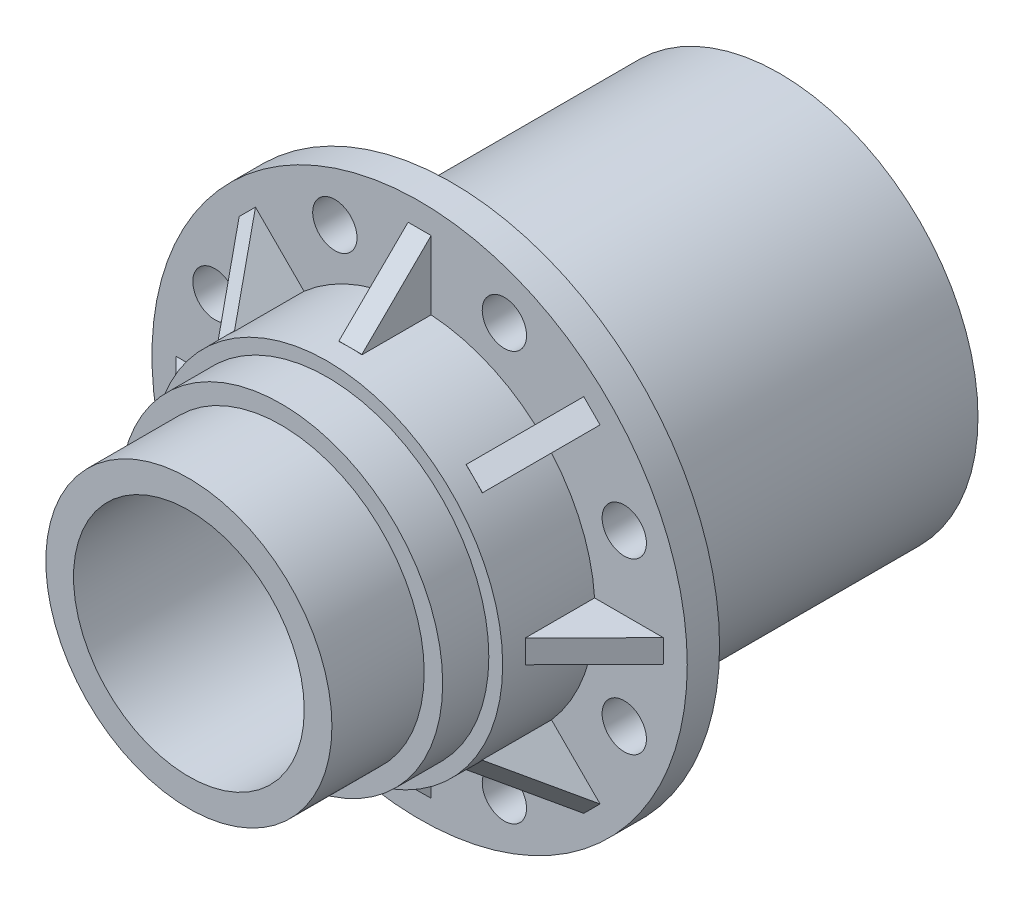
SolidWorks part; units mm, degrees
material "Plain Carbon Steel"
ref_plane "Front Plane" through (0, 0, 0) normal (1, 0, 0) x (0, 1, 0)
ref_plane "Top Plane" through (0, 0, 0) normal (0, 0, 1) x (0, 1, 0)
ref_plane "Right Plane" through (0, 0, 0) normal (0, 1, 0) x (-1, 0, 0)
sketch "Sketch2" plane through (0, 0, 0) normal (0, 0, 1) x (0, 1, 0)
  circle A0 centre (0, 0) radius 290
  circle A2 centre (0, 0) radius 215
  circle A3 centre (0, 0) radius 190
  circle A4 centre (0, 0) radius 155
  circle A5 centre (0, 0) radius 105
  circle A6 centre (0, 0) radius 80
  circle A7 centre (0, 0) radius 125
  dimension "D1" = 580
  dimension "D2" = 430
  dimension "D3" = 380
  dimension "D4" = 310
  dimension "D5" = 210
  dimension "D6" = 160
  dimension "D7" = 250
extrude "Boss-Extrude1" add sketch "Sketch2" against normal blind 390 contours A2 A3 | A3 A4 region at (0, -208.9189, 0) region at (0, -184.626, 0)
extrude "Boss-Extrude2" add sketch "Sketch2<3>" against normal blind 315 contours A4 A5 region at (0, -150.6159, 0)
sketch "Sketch2<3>" plane through (0, 0, 0) normal (0, 0, 1) x (0, 1, 0) same geometry as "Sketch2"
extrude "Boss-Extrude4" add sketch "Sketch2<5>" against normal blind 190 contours A7 A5 | A5 A6 region at (0, -102.0302, 0) region at (0, -121.4645, 0)
sketch "Sketch2<5>" plane through (0, 0, 0) normal (0, 0, 1) x (0, 1, 0) same geometry as "Sketch2"
extrude "Cut-Extrude1" cut sketch "Sketch2<6>" against normal blind 165 contours A5 A6 | A7 A5 region at (0, -102.0302, 0) region at (0, -121.4645, 0)
sketch "Sketch2<6>" plane through (0, 0, 0) normal (0, 0, 1) x (0, 1, 0) same geometry as "Sketch2"
extrude "Boss-Extrude5" add sketch "Sketch2<7>" along normal blind 165 from offset 165 contours A7 A5 region at (0, -121.4645, 0) offset against normal yes
sketch "Sketch2<7>" plane through (0, 0, 0) normal (0, 0, 1) x (0, 1, 0) same geometry as "Sketch2"
extrude "Cut-Extrude2" cut sketch "Sketch2<9>" along normal blind 165 draft 8.746 from offset 165 contours A5 A6 region at (0, -102.0302, 0) draft outward yes offset against normal yes
sketch "Sketch2<9>" plane through (0, 0, 0) normal (0, 0, 1) x (0, 1, 0) same geometry as "Sketch2"
extrude "Boss-Extrude6" add sketch "Sketch2<10>" against normal blind 165 contours A4 A7 region at (0, -150.6159, 0)
sketch "Sketch2<10>" plane through (0, 0, 0) normal (0, 0, 1) x (0, 1, 0) same geometry as "Sketch2"
extrude "Cut-Extrude3" cut sketch "Sketch2<12>" against normal blind 60 contours A2 A3 region at (0, -208.9189, 0)
sketch "Sketch2<12>" plane through (0, 0, 0) normal (0, 0, 1) x (0, 1, 0) same geometry as "Sketch2"
extrude "Boss-Extrude7" add sketch "Sketch2<13>" against normal blind 35 contours A7 A5 | A4 A7 | A3 A4 | A2 A3 | A0 A2 | A5 A6 region at (0, -281.7976, 0) region at (0, -208.9189, 0) region at (0, -184.626, 0) region at (0, -150.6159, 0) region at (0, -102.0302, 0) region at (0, -121.4645, 0)
sketch "Sketch2<13>" plane through (0, 0, 0) normal (0, 0, 1) x (0, 1, 0) same geometry as "Sketch2"
sketch "Sketch3" plane through (0, 0, 0) normal (0, 0, 1) x (1, 0, 0)
  circle A0 centre (0, 0) radius 80
  circle A1 centre (0, 0) radius 125
  circle A2 centre (0, 0) radius 155
  circle A3 centre (0, 0) radius 175
  circle A4 centre (0, 0) radius 190
  circle A5 centre (0, 0) radius 290
  dimension "D1" = 160
  dimension "D2" = 250
  dimension "D3" = 310
  dimension "D4" = 350
  dimension "D5" = 380
  dimension "D6" = 580
extrude "Boss-Extrude8" add sketch "Sketch3" along normal blind 100 contours A2 A1 | A3 A2 | A4 A3 region at (-150.6159, 0, 0) region at (-170.0503, 0, 0) region at (-184.626, 0, 0)
extrude "Boss-Extrude10" add sketch "Sketch3<5>" along normal blind 150 contours A2 A1 | A3 A2 region at (-150.6159, 0, 0) region at (-170.0503, 0, 0)
sketch "Sketch3<5>" plane through (0, 0, 0) normal (0, 0, 1) x (1, 0, 0) same geometry as "Sketch3"
extrude "Boss-Extrude11" add sketch "Sketch3<6>" along normal blind 250 contours A2 A1 region at (-150.6159, 0, 0)
sketch "Sketch3<6>" plane through (0, 0, 0) normal (0, 0, 1) x (1, 0, 0) same geometry as "Sketch3"
sketch "Sketch4" plane through (0, 0, 0) normal (0, 0, 1) x (1, 0, 0)
  line L0 (0, 0) -> (221.7311, 91.844)
  circle A0 centre (0, 0) radius 240
  circle A1 centre (221.7311, 91.844) radius 24
  dimension "D1" = 480
  dimension "D2" = 48
extrude "Cut-Extrude5" cut sketch "Sketch4" against normal up to next contours L0 A1 A0 | A0 A1 L0 | A1 region at (208.2905, 97.1186, 0) region at (215.9568, 78.6104, 0)
pattern_circular "CirPattern2" count 8 every 45 about axis through (0, 0, 0) along (0, 0, 1) of "Cut-Extrude5"
sketch "Sketch6" plane through (0, 0, 0) normal (1, 0, 0) x (0, 1, 0)
  line L5 (-190, 75) -> (-264, 0)
  line L6 (-190, 0) -> (-264, 0)
  line L7 (-190, 0) -> (-190, 75)
  line L10 (-190, 75) -> (-168, 75)
  line L11 (-168, 75) -> (-168, 0)
  line L12 (290, 0) -> (-290, 0) construction
  line L13 (-168, 0) -> (-190, 0)
  dimension "D1" = 74
  dimension "D2" = 75
  dimension "D3" = 22
extrude "Boss-Extrude12" add sketch "Sketch6" along normal blind 12.5 and the other way blind 12.5 contours L6 L7 L5 | L13 L11 L10 L7 region at (0, -214.6667, 25) region at (0, -179, 37.5)
pattern_circular "CirPattern3" count 8 every 45 about axis through (0, 0, 0) along (0, 0, 1) of "Boss-Extrude12"
